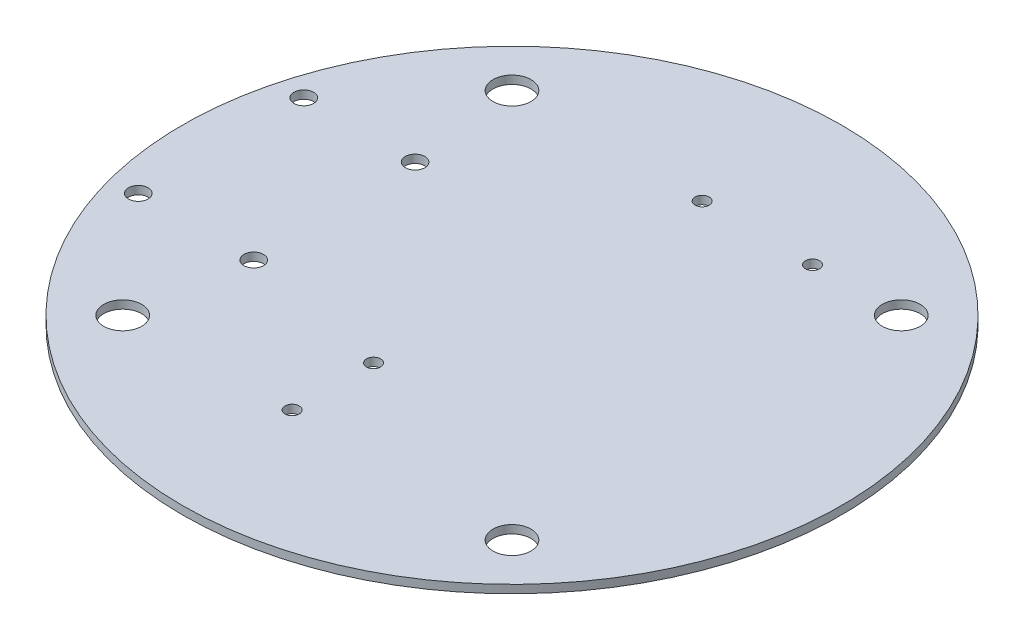
SolidWorks part; units mm, degrees
ref_plane "Front Plane" through (0, 0, 0) normal (0, 0, 1) x (1, 0, 0)
ref_plane "Top Plane" through (0, 0, 0) normal (0, 1, 0) x (1, 0, 0)
ref_plane "Right Plane" through (0, 0, 0) normal (1, 0, 0) x (0, 0, -1)
sketch "Sketch1" plane through (0, 0, 0) normal (0, 1, 0) x (1, 0, 0)
  circle A0 centre (0, 0) radius 60.7
  dimension "PCBdiam" = 121.4
extrude "Boss-Extrude1" add sketch "Sketch1" along normal blind 1.5
hole_wizard "M6 Clearance Hole1" positions "Sketch2" profile "Sketch4" hole size "M6" standard "ANSI Metric" end condition through all
sketch "Sketch2" plane through (0, 1.5, 0) normal (0, 1, 0) x (1, 0, 0)
  line L0 (0, 0) -> (-28.5457, 28.5457) construction
  line L1 (-35.8503, -35.8503) -> (0, 0) construction
  line L3 (0, 0) -> (-73.422, 0) construction
  circle A0 centre (0, 0) radius 60.7 construction
  ellipse E2 centre (-116.4291, -176.9435) end of major axis (-117.7556, -176.0714) minor radius 1.3748
  ellipse E3 centre (-116.4291, -176.9435) end of major axis (-115.1026, -177.8157) minor radius 1.3748
  point P7 (-35.8503, -35.8503)
  dimension "D1" = 0
  dimension "holeRadius" = 50.7
  dimension "D2" = 45
sketch "Sketch4" plane through (-35.8503, 1.5, 35.8503) normal (1, 0, 0) x (0, 0, 1)
  line L0 (0, 0) -> (0, 1.5)
  line L1 (0, 1.5) -> (3.5, 1.5)
  line L2 (3.5, 1.5) -> (3.5, 0)
  line L5 (3.5, 0) -> (0, 0)
  line L11 (0, -6.35) -> (0, 107.95) construction
  dimension "Thru Hole Dia." = 7
  dimension "Thru Hole Depth" = 1.5
pattern_circular "CirPattern1" count 4 over 360 about axis through (0, 1.5, 0) along (0, -1, 0) of "M6 Clearance Hole1"
sketch "Teensy Outline" plane through (0, 1.5, 0) normal (0, 1, 0) x (1, 0, 0)
  line L1 (-27.654, 45.7) -> (-10, 45.7)
  line L2 (-27.654, 45.7) -> (-27.654, -12.72)
  line L3 (-27.654, -12.72) -> (-10, -12.72)
  line L4 (-10, 45.7) -> (-10, -12.72)
  circle A1 centre (0, 0) radius 60.7 construction
  dimension "D1" = 17.654
  dimension "D2" = 58.42
  dimension "D3" = 10
  dimension "D4" = 15
sketch "BMP390 Outline" plane through (0, 1.5, 0) normal (0, 1, 0) x (1, 0, 0)
  line L0 (19.61, 49.7) -> (-3.25, 49.7) construction
  line L2 (22.15, 51.04) -> (-3.25, 51.04)
  line L3 (-3.25, 51.04) -> (-3.25, 33.26)
  line L4 (22.15, 33.26) -> (-3.25, 33.26)
  line L6 (22.15, 51.04) -> (22.15, 33.26)
  line L7 (19.61, 49.7) -> (19.61, 33.26) construction
  line L8 (-27.654, 45.7) -> (-10, 45.7) construction
  line L9 (-10, 45.7) -> (-10, -12.72) construction
  dimension "D1" = 17.78
  dimension "D2" = 25.4
  dimension "D3" = 1.34
  dimension "D4" = 4
  dimension "D5" = 6.75
  dimension "D6" = 5.08
sketch "NEO-6M Outline" plane through (0, 1.5, 0) normal (0, 1, 0) x (1, 0, 0)
  line L0 (-48.84, 17.78) -> (-48.84, 15.24) construction
  line L1 (-56.34, 17.78) -> (-30, 17.78)
  line L2 (-56.34, 17.78) -> (-56.34, -17.78)
  line L3 (-56.34, -17.78) -> (-30, -17.78)
  line L4 (-30, 17.78) -> (-30, -17.78)
  line L5 (-48.84, 15.24) -> (-37.5, 15.24) construction
  line L6 (-37.5, 15.24) -> (-37.5, 17.78) construction
  point P4 (-30, 0)
  point P9 (-43.17, 15.24)
  point P11 (-43.17, 17.78)
  dimension "D1" = 26.34
  dimension "D2" = 35.56
  dimension "D3" = 30
  dimension "D4" = 7.5
  dimension "D5" = 2.54
sketch "Xbee outline" plane through (0, 1.5, 0) normal (0, 1, 0) x (1, 0, 0)
  line L0 (9, 0) -> (26, 0) construction
  line L1 (26, -4.625) -> (26, 4.625)
  line L2 (26, 4.625) -> (19.5, 12.25)
  line L3 (19.5, 12.25) -> (-7, 12.25)
  line L4 (-7, 12.25) -> (-7, -12.25)
  line L5 (19.5, -12.25) -> (-7, -12.25)
  line L6 (26, -4.625) -> (19.5, -12.25)
  line L7 (0, 0) -> (72.9219, 0) construction
  line L9 (-10, 45.7) -> (-10, -12.72) construction
  line L10 (61, 5.5) -> (26, 5.5) construction
  line L11 (61, 5.5) -> (61, -5.5) construction
  line L12 (61, -5.5) -> (26, -5.5) construction
  line L13 (26, 5.5) -> (26, -5.5) construction
  point P7 (-7, 0)
  point P11 (26, 0)
  dimension "D1" = 24.5
  dimension "D2" = 33
  dimension "D3" = 26.5
  dimension "D4" = 9.25
  dimension "D5" = 16
  dimension "D6" = 35
  dimension "D7" = 11
  dimension "D8" = 0
  dimension "D9" = 3
sketch "Accel, gyro outline" plane through (0, 1.5, 0) normal (0, 1, 0) x (1, 0, 0)
  line L0 (47.32, 26.44) -> (27, 26.44) construction
  line L1 (52.4, 27.78) -> (27, 27.78)
  line L2 (27, 27.78) -> (27, 10)
  line L3 (52.4, 10) -> (27, 10)
  line L4 (52.4, 27.78) -> (52.4, 10)
  line L5 (47.32, 26.44) -> (47.32, 11.34) construction
  line L6 (27, 18.89) -> (52.4, 18.89) construction
  line L7 (47.32, 11.34) -> (27, 11.34) construction
  dimension "D1" = 17.78
  dimension "D2" = 25.4
  dimension "D3" = 1.34
  dimension "D4" = 5.08
  dimension "D5" = 10
  dimension "D6" = 27
sketch "Airspeed sensor outline" plane through (0, 1.5, 0) normal (0, 1, 0) x (1, 0, 0)
  line L0 (-22.654, -23.8503) -> (-29.154, -23.8503) construction
  line L1 (-22.654, -17.8503) -> (-2.654, -17.8503)
  line L2 (-22.654, -17.8503) -> (-22.654, -37.8503)
  line L3 (-22.654, -37.8503) -> (-2.654, -37.8503)
  line L4 (-2.654, -17.8503) -> (-2.654, -37.8503)
  line L5 (-29.154, -23.8503) -> (-29.154, -31.8503) construction
  line L6 (-29.154, -31.8503) -> (-22.654, -31.8503) construction
  line L7 (-27.654, 45.7) -> (-27.654, -12.72) construction
  circle A0 centre (-35.8503, -35.8503) radius 3.5 construction
  point P8 (-29.154, -27.8503)
  point P9 (-22.654, -27.8503)
  dimension "D1" = 20
  dimension "D2" = 20
  dimension "D3" = 6.5
  dimension "D4" = 8
  dimension "D5" = 5
  dimension "D6" = 2
hole_wizard "M2 Clearance Hole1" positions "Sketch20" profile "Sketch19" hole size "M2" standard "ANSI Metric" end condition through all
sketch "Sketch20" plane through (0, 1.5, 0) normal (0, 1, 0) x (1, 0, 0)
  circle A0 centre (-0.71, 35.73) radius 1.2493 construction
  circle A1 centre (19.61, 35.73) radius 1.2493 construction
  circle A2 centre (-5.154, -20.3503) radius 1.25 construction
  circle A3 centre (-5.154, -20.3503) radius 1.25 construction
  circle A4 centre (-5.154, -35.3503) radius 1.25 construction
  circle A5 centre (-5.154, -35.3503) radius 1.25 construction
  point P1 (-0.71, 35.73)
  point P7 (19.61, 35.73)
  point P13 (-5.154, -20.3503)
  point P16 (-5.154, -35.3503)
sketch "Sketch19" plane through (-0.71, 1.5, -35.73) normal (1, 0, 0) x (0, 0, 1)
  line L0 (0, 0) -> (0, 1.5)
  line L1 (0, 1.5) -> (1.3, 1.5)
  line L2 (1.3, 1.5) -> (1.3, 0)
  line L5 (1.3, 0) -> (0, 0)
  line L11 (0, -6.35) -> (0, 107.95) construction
  dimension "Thru Hole Dia." = 2.6
  dimension "Thru Hole Depth" = 1.5
hole_wizard "M3 Clearance Hole2" positions "Sketch21" profile "Sketch22" hole size "M3" standard "ANSI Metric" end condition through all
sketch "Sketch21" plane through (0, 1.5, 0) normal (0, 1, 0) x (1, 0, 0)
  point P0 (-53.8645, 15.5117)
  point P3 (-53.8645, -14.9683)
  point P6 (-32.6045, -14.9683)
  point P9 (-33.3665, 15.5117)
sketch "Sketch22" plane through (-53.8645, 1.5, -15.5117) normal (1, 0, 0) x (0, 0, 1)
  line L0 (0, 0) -> (0, 1.5)
  line L1 (0, 1.5) -> (1.8, 1.5)
  line L2 (1.8, 1.5) -> (1.8, 0)
  line L5 (1.8, 0) -> (0, 0)
  line L11 (0, -6.35) -> (0, 107.95) construction
  dimension "Thru Hole Dia." = 3.6
  dimension "Thru Hole Depth" = 1.5
